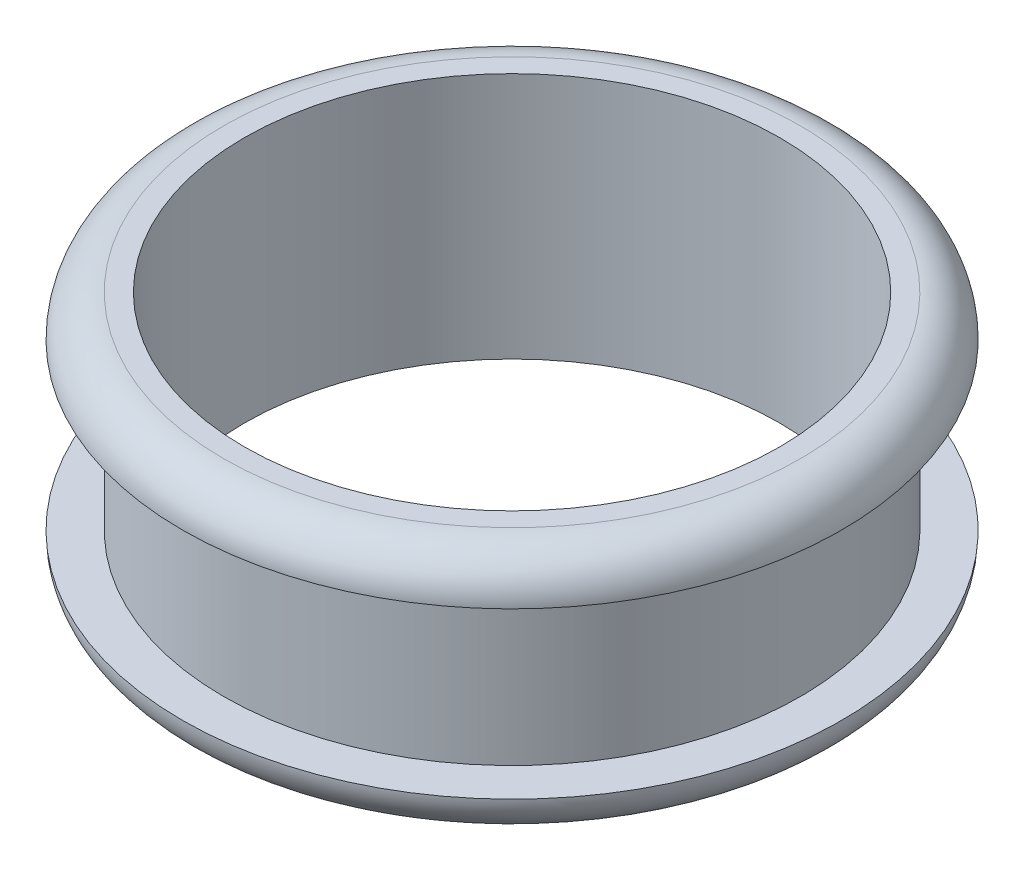
SolidWorks part; units mm, degrees
material "Silicon Rubber"
ref_plane "Front Plane" through (0, 0, 0) normal (0, 0, 1) x (1, 0, 0)
ref_plane "Top Plane" through (0, 0, 0) normal (0, 1, 0) x (1, 0, 0)
ref_plane "Right Plane" through (0, 0, 0) normal (1, 0, 0) x (0, 0, -1)
sketch "Sketch1" plane through (0, 0, 0) normal (0, 1, 0) x (1, 0, 0)
  circle A0 centre (0, 0) radius 4
  dimension "D1" = 8
extrude "Boss-Extrude1" add sketch "Sketch1" along normal mid plane 3
sketch "Sketch2" plane through (0, 0, 0) normal (0, 1, 0) x (1, 0, 0)
  circle A0 centre (0, 0) radius 3.25
  dimension "D1" = 6.5
extrude "Cut-Extrude1" cut sketch "Sketch2" against normal through all both and the other way through all
sketch "Sketch4" plane through (0, 0, 0) normal (1, 0, 0) x (0, 0, -1)
  line L0 (-4, 1.5) -> (-4, -1.5) construction
  line L1 (-4, 1) -> (-3.5, 1)
  line L2 (-4, 1) -> (-4, -1)
  line L3 (-4, -1) -> (-3.5, -1)
  line L4 (-3.5, 1) -> (-3.5, -1)
  line L5 (4, 1.5) -> (-4, 1.5) construction
  line L6 (-4, -1.5) -> (4, -1.5) construction
  line L7 (0, 1.1157) -> (0, -1.0758) construction
  dimension "D1" = 0.5
  dimension "D2" = 0.5
  dimension "D3" = 0.5
revolve "Cut-Revolve1" cut sketch "Sketch4" angle 360 about L7
fillet "Fillet1" radius 0.5 2 edges at (0, -1.5, 4) (0, 1.5, 4)
